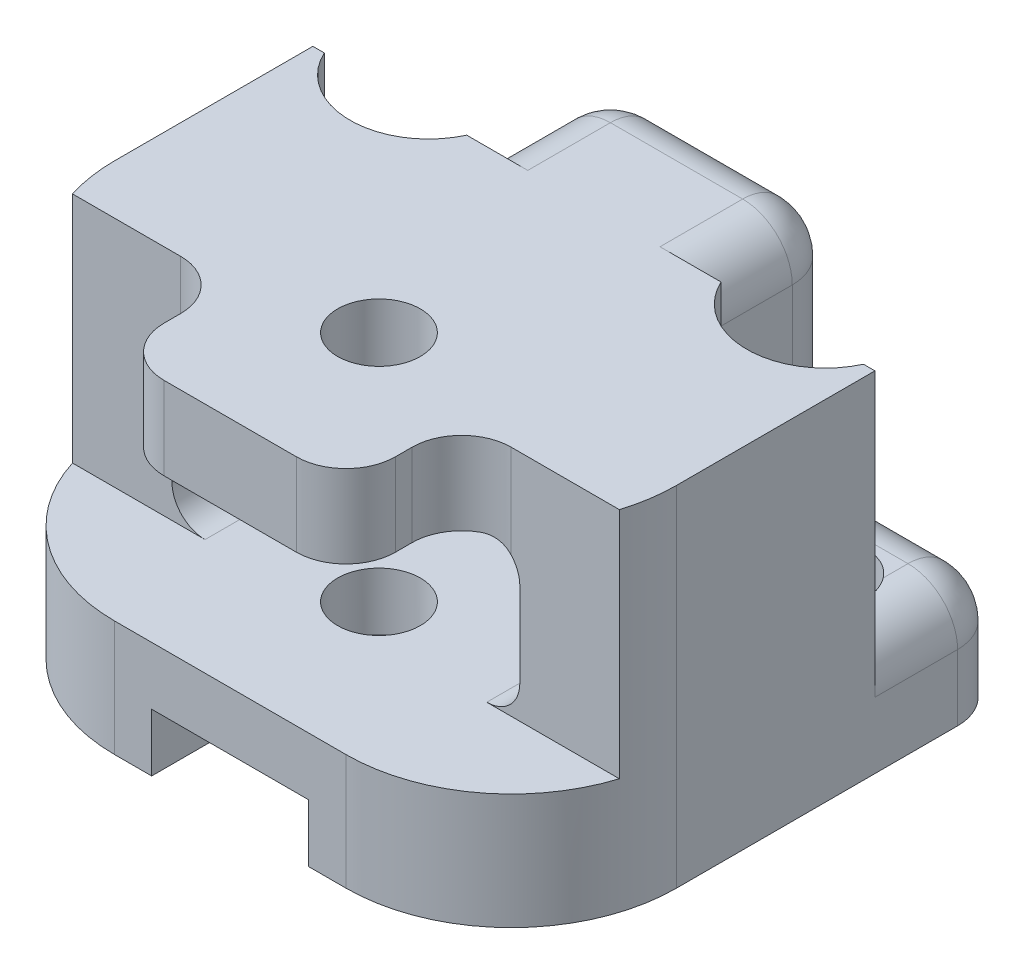
SolidWorks part; units mm, degrees
ref_plane "Alzado" through (0, 0, 0) normal (0, 0, 1) x (1, 0, 0)
ref_plane "Planta" through (0, 0, 0) normal (0, 1, 0) x (1, 0, 0)
ref_plane "Vista lateral" through (0, 0, 0) normal (1, 0, 0) x (0, 0, -1)
sketch "Croquis1" plane through (0, 0, 0) normal (0, 1, 0) x (1, 0, 0)
  line L0 (-34, -6) -> (-29, -6) construction
  line L1 (0, 0) -> (-34, 0)
  line L2 (0, 0) -> (0, -30)
  line L3 (0, -30) -> (-34, -30)
  line L4 (-34, 0) -> (-34, -30)
  line L5 (-29, -6) -> (-29, 0) construction
  line L6 (-17, 0) -> (-17, -2.6345) construction
  line L8 (0, -15) -> (-3.207, -15) construction
  circle A0 centre (-29, -6) radius 2.5
  circle A1 centre (-5, -6) radius 2.5
  circle A2 centre (-5, -24) radius 2.5 construction
  circle A3 centre (-29, -24) radius 2.5 construction
  dimension "D5" = 5
  dimension "D1" = 30
  dimension "D2" = 34
  dimension "D3" = 6
  dimension "D4" = 5
extrude "Saliente-Extruir1" add sketch "Croquis1" along normal blind 7
fillet "Redondeo1" radius 10 2 edges at (0, 3.5, 30) (-34, 3.5, 30)
sketch "Croquis2" plane through (0, 7, 0) normal (0, 1, 0) x (1, 0, 0)
  line L0 (-24, 0) -> (-24, -30)
  line L1 (-24, -30) -> (-10, -30)
  line L2 (-10, -30) -> (-10, 0)
  line L3 (-10, 0) -> (-24, 0)
  line L4 (0, 0) -> (-34, 0) construction
extrude "Saliente-Extruir2" add sketch "Croquis2" along normal blind 14.1
sketch "Croquis3" plane through (-24, 0, 0) normal (-1, 0, 0) x (0, 0, 1)
  line L0 (9, 7) -> (30, 7)
  line L1 (23, 16.1) -> (9, 16.1)
  line L4 (5, 12.1) -> (5, 11)
  line L5 (0, 21.1) -> (30, 21.1) construction
  line L6 (30, 16.1) -> (23, 16.1)
  line L10 (5, 11.55) -> (0, 9.55) construction
  line L13 (0, 21.1) -> (0, 7) construction
  line L17 (30, 16.1) -> (30, 7)
  arc A0 (9, 7) -> (5, 11) centre (9, 11) cw
  arc A1 (9, 16.1) -> (5, 12.1) centre (9, 12.1) ccw
  point P16 (5, 16.1)
  dimension "D4" = 4
  dimension "D1" = 18
  dimension "D3" = 5
  dimension "D5" = 9.1
extrude "Cortar-Extruir1" cut sketch "Croquis3" against normal up to next
sketch "Croquis4" plane through (0, 21.1, 0) normal (0, 1, 0) x (1, 0, 0)
  line L2 (-17, -21) -> (-17, -30) construction
  line L3 (-24, -30) -> (-10, -30) construction
  circle A0 centre (-17, -21) radius 2.5
  point P4 (0, 0)
  point P9 (0, 0)
  point P12 (0, 0)
  dimension "D1" = 5
  dimension "D2" = 9
extrude "Cortar-Extruir2" cut sketch "Croquis4" against normal up to surface (21.1 mm away) up to face at (-29, 0, 8.5)
sketch "Croquis5" plane through (0, 0, 30) normal (0, 0, 1) x (1, 0, 0)
  line L0 (-24, 0) -> (-10, 0) construction
  line L1 (-21.75, 0) -> (-12.25, 0)
  line L2 (-21.75, 0) -> (-21.75, 3.5)
  line L3 (-21.75, 3.5) -> (-12.25, 3.5)
  line L4 (-12.25, 0) -> (-12.25, 3.5)
  line L5 (-24, 7) -> (-24, 0) construction
  line L6 (-12.25, 1.75) -> (-10, 1.75) construction
  line L7 (-10, 0) -> (-10, 7) construction
  dimension "D1" = 3.5
  dimension "D2" = 9.5
  dimension "D3" = 2.25
extrude "Cortar-Extruir3" cut sketch "Croquis5" against normal blind 20
sketch "Croquis6" plane through (0, 21.1, 0) normal (0, 1, 0) x (1, 0, 0)
  line L0 (-24, -23) -> (-33.5394, -23)
  line L1 (-10, -23) -> (-0.4606, -23)
  line L3 (-17, -23) -> (-17, -21.4511) construction
  line L5 (-34, 0) -> (-34, -20) construction
  line L7 (-24, -23) -> (-24, -8)
  line L8 (-24, -8) -> (-34, -8)
  line L9 (-34, -20) -> (-34, -8)
  line L15 (-24, -23) -> (-10, -23) construction
  line L18 (0, -20) -> (0, -8)
  line L19 (-10, -8) -> (0, -8)
  line L20 (-10, -23) -> (-10, -8)
  arc A1 (-34, -20) -> (-24, -30) centre (-24, -20) ccw construction
  arc A2 (-34, -20) -> (-33.5394, -23) centre (-24, -20) ccw
  arc A3 (0, -20) -> (-0.4606, -23) centre (-10, -20) cw
extrude "Saliente-Extruir3" add sketch "Croquis6" against normal up to surface (5 mm away) up to face at (-17, 16.1, 23.5)
sketch "Croquis7" plane through (0, 16.1, 0) normal (0, -1, 0) x (1, 0, 0)
  line L0 (-24, 8.5) -> (-27.52, 8.5) construction
  line L1 (-24, 8) -> (-24, 9) construction
  line L2 (-34, 8) -> (-24, 8) construction
  line L3 (-27.52, 8) -> (-34, 8)
  line L4 (-27.52, 8) -> (-27.52, 23)
  line L5 (-27.52, 23) -> (-33.5394, 23)
  line L6 (-34, 8) -> (-34, 20)
  line L7 (-17, 10) -> (-17, 11.844) construction
  line L8 (-12.25, 10) -> (-21.75, 10) construction
  line L13 (0, 8) -> (0, 20)
  line L14 (-6.48, 23) -> (-0.4606, 23)
  line L15 (-6.48, 8) -> (-6.48, 23)
  line L16 (-6.48, 8) -> (0, 8)
  arc A0 (-24, 30) -> (-34, 20) centre (-24, 20) ccw construction
  arc A1 (-33.5394, 23) -> (-34, 20) centre (-24, 20) ccw
  arc A2 (-0.4606, 23) -> (0, 20) centre (-10, 20) cw
  dimension "D1" = 3.52
extrude "Saliente-Extruir4" add sketch "Croquis7" along normal up to surface (9.1 mm away) up to face at (-17, 7, 18.5)
sketch "Croquis8" plane through (0, 21.1, 0) normal (0, 1, 0) x (1, 0, 0)
  line L16 (-17, 0) -> (-17, -3.5124) construction
  line L17 (-10, 0) -> (-24, 0) construction
  circle A8 centre (-29, -6) radius 4.75
  circle A9 centre (-5, -6) radius 4.75
  dimension "D1" = 9.5
extrude "Cortar-Extruir4" cut sketch "Croquis8" against normal up to surface (14.1 mm away) up to face at (-17, 7, 18.5)
sketch "Croquis9" plane through (0, 21.1, 0) normal (0, 1, 0) x (1, 0, 0)
  line L0 (-34, -8) -> (-34, -20) construction
  line L1 (-34, -8.95) -> (-32, -8.95)
  line L2 (-34, -8.95) -> (-34, -19.05)
  line L3 (-34, -19.05) -> (-32, -19.05)
  line L4 (-32, -8.95) -> (-32, -19.05)
  line L5 (-17, -23) -> (-17, -20.4705) construction
  line L7 (-34, -14) -> (-32.7186, -14) construction
  line L8 (0, -19.05) -> (-2, -19.05)
  line L9 (-2, -8.95) -> (-2, -19.05)
  line L10 (0, -8.95) -> (-2, -8.95)
  line L11 (0, -8.95) -> (0, -19.05)
  point P10 (-34, -14)
  dimension "D1" = 10.1
  dimension "D2" = 2
fillet "Redondeo5" radius 2 4 edges at (-6.48, 16.1, 16.7568) (-6.48, 7, 16.7568) (-27.52, 7, 16.7568) (-27.52, 16.1, 16.7568)
fillet "Redondeo6" radius 3 4 edges at (-24, 18.6, 23) (-10, 18.6, 23) (-10, 18.6, 30) (-24, 18.6, 30)
fillet "Redondeo7" radius 3 11 edges at (0, 3.5, 0) (-34, 3.5, 0) (-34, 7, 4) (0, 7, 4) (-5, 7, 0) (-29, 7, 0) (-24, 21.1, 4) (-10, 21.1, 4) (-10, 14.05, 0) (-17, 21.1, 0) (-24, 14.05, 0)
